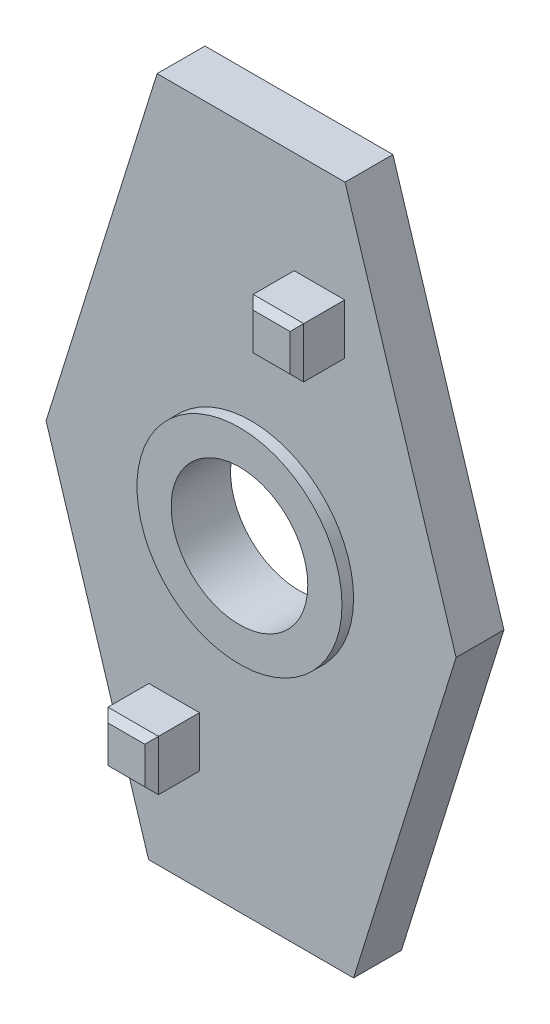
SolidWorks part; units mm, degrees
ref_plane "Front Plane" through (0, 0, 0) normal (0, 0, 1) x (1, 0, 0)
ref_plane "Top Plane" through (0, 0, 0) normal (0, 1, 0) x (1, 0, 0)
ref_plane "Right Plane" through (0, 0, 0) normal (1, 0, 0) x (0, 0, -1)
sketch "Sketch1" plane through (0, 0, 0) normal (0, 0, 1) x (1, 0, 0)
  line L0 (-30, 0) -> (-15, -48.1183)
  line L1 (-15, -48.1183) -> (15, -48.1183)
  line L2 (15, -48.1183) -> (30, 0)
  line L3 (30, 0) -> (15, 48.1183)
  line L4 (15, 48.1183) -> (-15, 48.1183) construction
  line L5 (-15, 48.1183) -> (-30, 0)
  line L6 (0, 48.1183) -> (0, -48.1183) construction
  line L7 (-2, -15.1183) -> (2, -15.1183)
  line L8 (2, -15.1183) -> (2, -48.1183) construction
  line L9 (-15, 48.1183) -> (-13.7531, 52.1183)
  line L10 (-13.7531, 52.1183) -> (13.7531, 52.1183)
  line L11 (13.7531, 52.1183) -> (15, 48.1183)
  line L12 (-15, -48.1183) -> (-14.95, -48.1183) construction
  line L13 (-14.95, -48.1183) -> (-14.95, -33.1683) construction
  line L14 (13.7531, 52.1183) -> (13.7031, 52.1183) construction
  line L15 (13.7031, 52.1183) -> (13.7031, 37.1683) construction
  line L17 (13.7031, 37.1683) -> (6.3031, 37.1683)
  line L18 (13.7031, 37.1683) -> (13.7031, 29.7683)
  line L19 (13.7031, 29.7683) -> (6.3031, 29.7683)
  line L20 (6.3031, 37.1683) -> (6.3031, 29.7683)
  line L21 (-14.95, -33.1683) -> (-7.55, -33.1683)
  line L22 (-14.95, -33.1683) -> (-14.95, -25.7683)
  line L23 (-14.95, -25.7683) -> (-7.55, -25.7683)
  line L24 (-7.55, -33.1683) -> (-7.55, -25.7683)
  circle A0 centre (0, 0) radius 15.25 construction
  circle A1 centre (0, 0) radius 10
  circle A2 centre (0, 0) radius 15
  point P14 (0, -15.1183)
  dimension "D3" = 30.5
  dimension "D4" = 4
  dimension "D7" = 20
  dimension "D16" = 30
  dimension "D1" = 30
  dimension "D2" = 60
  dimension "D5" = 33
  dimension "D6" = 4
  dimension "D8" = 7.4
  dimension "D9" = 7.4
  dimension "D10" = 0.05
  dimension "D11" = 7.4
  dimension "D12" = 7.4
  dimension "D13" = 0.05
  dimension "D14" = 14.95
  dimension "D15" = 14.95
extrude "Boss-Extrude1" add sketch "Sketch1" against normal blind 7 contours L11 L10 L9 L5 L0 L1 L2 L3 A1 L24 L21 L22 L23 L20 L17 L18 L19 | L21 L24 L23 L22 | L17 L20 L19 L18 | A2 A1 region at (-21.3847, 23.7115, 0) region at (10.0031, 33.4683, 0) region at (-11.25, -29.4683, 0) region at (-14.5757, 0, 0)
extrude "Boss-Extrude2" add sketch "Sketch1<3>" along normal blind 7 contours L21 L24 L23 L22 | L17 L20 L19 L18 region at (10.0031, 33.4683, 0) region at (-11.25, -29.4683, 0)
sketch "Sketch1<3>" plane through (0, 0, 0) normal (0, 0, 1) x (1, 0, 0) same geometry as "Sketch1"
chamfer "Chamfer1" distance 1 angle 45 8 edges at (13.7031, 33.4683, 7) (10.0031, 29.7683, 7) (6.3031, 33.4683, 7) (10.0031, 37.1683, 7) (-14.95, -29.4683, 7) (-11.25, -25.7683, 7) (-7.55, -29.4683, 7) (-11.25, -33.1683, 7)
extrude "Boss-Extrude3" add sketch "Sketch1<4>" along normal blind 1.7 contours A2 A1 region at (-14.5757, 0, 0)
sketch "Sketch1<4>" plane through (0, 0, 0) normal (0, 0, 1) x (1, 0, 0) same geometry as "Sketch1"
